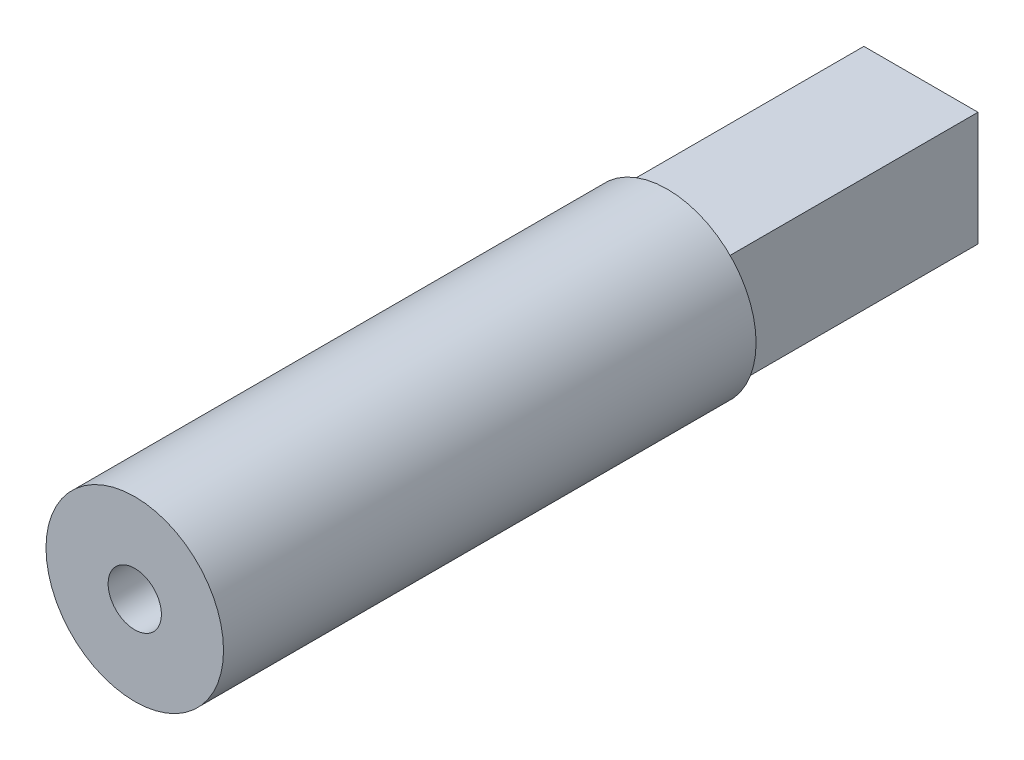
SolidWorks part; units mm, degrees
ref_plane "Front Plane" through (0, 0, 0) normal (0, 0, 1) x (1, 0, 0)
ref_plane "Top Plane" through (0, 0, 0) normal (0, 1, 0) x (1, 0, 0)
ref_plane "Right Plane" through (0, 0, 0) normal (1, 0, 0) x (0, 0, -1)
sketch "Sketch2" plane through (0, 0, 0) normal (0, 0, 1) x (1, 0, 0)
  circle A0 centre (0, 0) radius 3.5
extrude "Boss-Extrude1" add sketch "Sketch2" along normal blind 31
sketch "Sketch4" plane through (0, 0, 0) normal (0, 0, -1) x (-1, 0, 0)
  line L1 (-2.25, 2.25) -> (2.25, 2.25)
  line L2 (-2.25, 2.25) -> (-2.25, -2.25)
  line L3 (-2.25, -2.25) -> (2.25, -2.25)
  line L4 (2.25, 2.25) -> (2.25, -2.25)
  line L5 (-2.25, 2.25) -> (2.25, -2.25) construction
  line L6 (-2.25, -2.25) -> (2.25, 2.25) construction
  circle A1 centre (0, 0) radius 3.5
  circle A2 centre (0, 0) radius 3.5
  point P0 (0, 0)
  dimension "D1" = 4.5
  dimension "D2" = 4.5
  dimension "D3" = 0
extrude "Cut-Extrude1" cut sketch "Sketch4" against normal blind 10
sketch "Sketch7" plane through (0, 0, 31) normal (0, 0, 1) x (1, 0, 0)
  circle A0 centre (0, 0) radius 1.05
extrude "Cut-Extrude2" cut sketch "Sketch7" against normal blind 6
